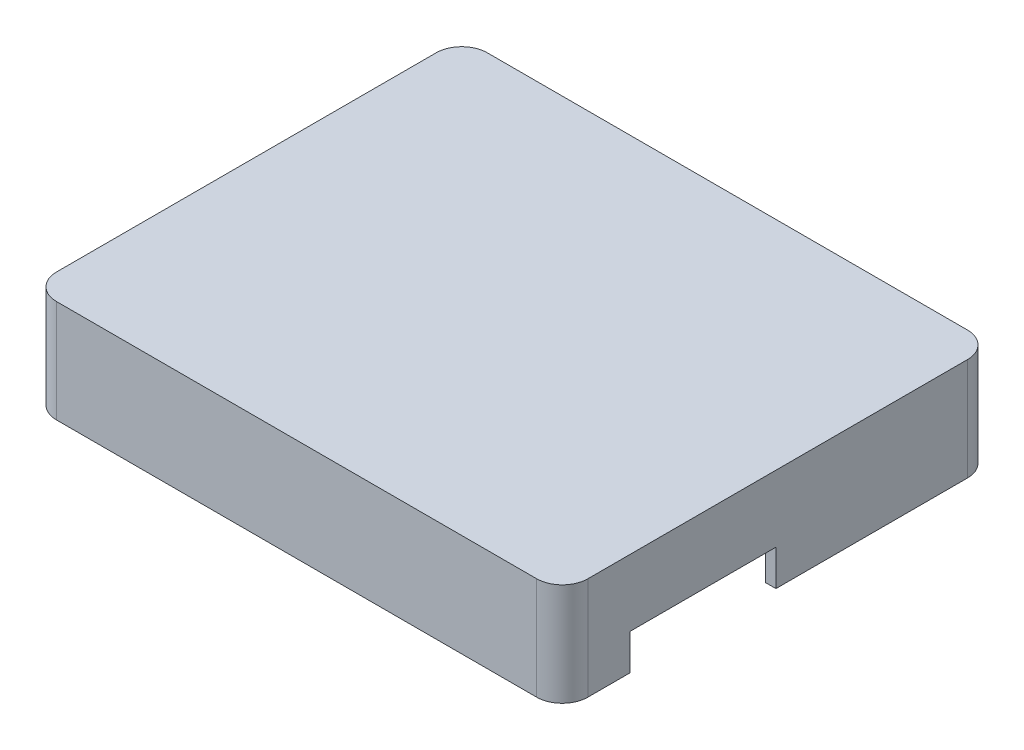
SolidWorks part; units mm, degrees
ref_plane "Front Plane" through (0, 0, 0) normal (0, 0, 1) x (1, 0, 0)
ref_plane "Top Plane" through (0, 0, 0) normal (0, 1, 0) x (1, 0, 0)
ref_plane "Right Plane" through (0, 0, 0) normal (1, 0, 0) x (0, 0, -1)
sketch "Sketch1" plane through (0, 0, 0) normal (0, 1, 0) x (1, 0, 0)
  line L0 (-36.1611, 34.3606) -> (-36.1611, -16.4394) construction
  line L1 (-38.7011, 34.3606) -> (24.5449, 34.3606)
  line L2 (-38.7011, 34.3606) -> (-38.7011, -16.4394)
  line L3 (-38.7011, -16.4394) -> (24.5449, -16.4394)
  line L4 (24.5449, 34.3606) -> (24.5449, -16.4394)
  line L5 (-38.7011, 31.8206) -> (24.5449, 31.8206) construction
  line L6 (22.0049, 34.3606) -> (22.0049, -16.4394) construction
  line L7 (-38.7011, -13.8994) -> (24.5449, -13.8994) construction
  line L8 (-7.0781, 31.8206) -> (-7.0781, -13.8994) construction
  line L9 (22.0049, 8.9606) -> (-36.1611, 8.9606) construction
  dimension "D1" = 63.246
  dimension "D2" = 50.8
  dimension "D3" = 2.54
  dimension "D4" = 2.54
  dimension "D5" = 2.54
  dimension "D6" = 2.54
sketch "Sketch4" plane through (0, 0, 0) normal (0, 1, 0) x (1, 0, 0)
  line L0 (-34.6003, 169.5077) -> (28.6457, 169.5077) construction
  dimension "D1" = 63.246
sketch "Sketch5" plane through (0, 0, 0) normal (0, 1, 0) x (1, 0, 0)
  line L8 (25.8149, -17.7094) -> (25.8149, 35.6306)
  line L9 (25.8149, 35.6306) -> (-39.9711, 35.6306)
  line L10 (-39.9711, 35.6306) -> (-39.9711, -17.7094)
  line L11 (-39.9711, -17.7094) -> (25.8149, -17.7094)
  line L12 (25.8149, -17.7094) -> (25.8149, 35.6306)
  line L13 (25.8149, 35.6306) -> (-39.9711, 35.6306)
  line L14 (-39.9711, 35.6306) -> (-39.9711, -17.7094)
  line L15 (-39.9711, -17.7094) -> (25.8149, -17.7094)
  dimension "D1" = 1.27
extrude "Boss-Extrude1" add sketch "Sketch5" along normal blind 12.7
sketch "Sketch7" plane through (0, 0, 0) normal (0, -1, 0) x (1, 0, 0)
  line L0 (-38.7011, -34.3606) -> (24.5449, -34.3606) construction
  line L1 (-38.7011, -34.3606) -> (-38.7011, 16.4394) construction
  line L2 (-38.7011, 16.4394) -> (24.5449, 16.4394) construction
  line L3 (24.5449, -34.3606) -> (24.5449, 16.4394) construction
  line L4 (-32.0336, -34.3606) -> (17.8774, -34.3606)
  line L5 (-38.7011, -27.6931) -> (-38.7011, 9.7719)
  line L6 (-32.0336, 16.4394) -> (17.8774, 16.4394)
  line L7 (24.5449, -27.6931) -> (24.5449, 9.7719)
  line L8 (-33.3036, 13.8994) -> (-33.3036, 15.1694)
  line L9 (-36.1611, 11.0419) -> (-37.4311, 11.0419)
  line L10 (-36.1611, -34.3606) -> (-36.1611, 16.4394) construction
  line L11 (-38.7011, 13.8994) -> (24.5449, 13.8994) construction
  line L12 (-38.7011, 13.8994) -> (24.5449, 13.8994) construction
  line L13 (-36.1611, -34.3606) -> (-36.1611, 16.4394) construction
  line L14 (-7.0781, 13.8994) -> (-7.0781, -34.3606) construction
  line L15 (19.1474, 13.8994) -> (19.1474, 15.1694)
  line L16 (22.0049, 11.0419) -> (23.2749, 11.0419)
  line L17 (-36.1611, -8.9606) -> (22.5409, -8.9606) construction
  line L18 (22.0049, -28.9631) -> (23.2749, -28.9631)
  line L19 (19.1474, -31.8206) -> (19.1474, -33.0906)
  line L20 (-33.3036, -31.8206) -> (-33.3036, -33.0906)
  line L21 (-36.1611, -28.9631) -> (-37.4311, -28.9631)
  circle A0 centre (-36.1611, 13.8994) radius 1.5875 construction
  arc A1 (-36.1611, 11.0419) -> (-33.3036, 13.8994) centre (-36.1611, 13.8994) ccw
  arc A2 (-38.7011, 9.7719) -> (-37.4311, 11.0419) centre (-37.4311, 9.7719) cw
  circle A3 centre (-36.1611, 13.8994) radius 2.8575 construction
  arc A4 (-33.3036, 15.1694) -> (-32.0336, 16.4394) centre (-32.0336, 15.1694) cw
  arc A5 (19.1474, 15.1694) -> (17.8774, 16.4394) centre (17.8774, 15.1694) ccw
  arc A6 (22.0049, 11.0419) -> (19.1474, 13.8994) centre (22.0049, 13.8994) cw
  arc A7 (24.5449, 9.7719) -> (23.2749, 11.0419) centre (23.2749, 9.7719) ccw
  arc A8 (24.5449, -27.6931) -> (23.2749, -28.9631) centre (23.2749, -27.6931) cw
  arc A9 (22.0049, -28.9631) -> (19.1474, -31.8206) centre (22.0049, -31.8206) ccw
  arc A10 (19.1474, -33.0906) -> (17.8774, -34.3606) centre (17.8774, -33.0906) cw
  arc A11 (-33.3036, -33.0906) -> (-32.0336, -34.3606) centre (-32.0336, -33.0906) ccw
  arc A12 (-36.1611, -28.9631) -> (-33.3036, -31.8206) centre (-36.1611, -31.8206) cw
  arc A13 (-38.7011, -27.6931) -> (-37.4311, -28.9631) centre (-37.4311, -27.6931) ccw
  point P12 (-33.371, 13.8931)
  dimension "D1" = 3.175
  dimension "D3" = 1.27
  dimension "D4" = 1.27
  dimension "D2" = 1.27
extrude "Cut-Extrude1" cut sketch "Sketch7" against normal blind 11.43
fillet "Fillet1" radius 3.175 4 edges at (-39.9711, 6.35, -35.6306) (25.8149, 6.35, -35.6306) (25.8149, 6.35, 17.7094) (-39.9711, 6.35, 17.7094)
sketch "Sketch8" plane through (0, 0, 0) normal (0, 1, 0) x (1, 0, 0)
  line L0 (-38.7011, 34.3606) -> (-38.7011, -16.4394) construction
  line L1 (-38.7011, -16.4394) -> (24.5449, -16.4394) construction
  line L2 (-38.7011, 34.3606) -> (24.5449, 34.3606) construction
  line L3 (24.5449, 34.3606) -> (24.5449, -16.4394) construction
  line L4 (-38.7011, 34.3606) -> (-38.7011, -16.4394)
  line L5 (-38.7011, -16.4394) -> (24.5449, -16.4394)
  line L6 (-38.7011, 34.3606) -> (24.5449, 34.3606)
  line L7 (24.5449, 34.3606) -> (24.5449, -16.4394)
extrude "Cut-Extrude2" cut sketch "Sketch8" along normal blind 1.5621
sketch "Sketch9" plane through (0, 0, 0) normal (0, 1, 0) x (1, 0, 0)
  line L0 (-38.7011, -16.4394) -> (24.5449, -16.4394) construction
  line L1 (34.2125, -9.3274) -> (18.9109, -9.3274)
  line L2 (34.2125, -9.3274) -> (34.2125, 8.7429)
  line L3 (34.2125, 8.7429) -> (18.9109, 8.7429)
  line L4 (18.9109, -9.3274) -> (18.9109, 8.7429)
  line L5 (-38.7011, -16.4394) -> (24.5449, -16.4394) construction
  dimension "D1" = 18.0703
  dimension "D2" = 15.3016
  dimension "D3" = 7.112
extrude "Cut-Extrude3" cut sketch "Sketch9" along normal blind 4.445
hole_wizard "Tap Drill for #4-40 Tap1" positions "Sketch11" profile "Sketch10" hole size "#4-40" standard "ANSI Inch"
sketch "Sketch11" plane through (0, 0, 0) normal (0, -1, 0) x (-1, 0, 0)
  line L1 (36.1611, 34.3606) -> (36.1611, -16.4394) construction
  line L2 (38.7011, -13.8994) -> (-24.5449, -13.8994) construction
  line L3 (36.1611, 34.3606) -> (36.1611, -16.4394) construction
  line L4 (38.7011, -13.8994) -> (-24.5449, -13.8994) construction
  point P12 (36.1611, -13.8994)
sketch "Sketch10" plane through (-36.1611, 0, 13.8994) normal (1, 0, 0) x (0, 0, -1)
  line L0 (0, 0) -> (0, 9.5692)
  line L1 (0, 9.5692) -> (1.1303, 8.89)
  line L2 (1.1303, 8.89) -> (1.1303, 0)
  line L5 (1.1303, 0) -> (0, 0)
  line L10 (0, 9.5692) -> (-1.1303, 8.89) construction
  line L11 (0, -6.35) -> (0, 107.95) construction
  dimension "Hole Dia." = 2.2606
  dimension "Hole Depth" = 8.89
  dimension "Drill Angle" = 118
ref_plane "Plane2" through (-7.0781, 0, 0) normal (1, 0, 0) x (0, 0, 1)
ref_plane "Plane3" through (0, 0, -8.9606) normal (0, 0, 1) x (-1, 0, 0)
mirror "Mirror1" about plane through (-7.0781, 0, 0) normal (1, 0, 0) of "Tap Drill for #4-40 Tap1"
mirror "Mirror2" about plane through (0, 0, -8.9606) normal (0, 0, 1) of "Mirror1", "Tap Drill for #4-40 Tap1"
